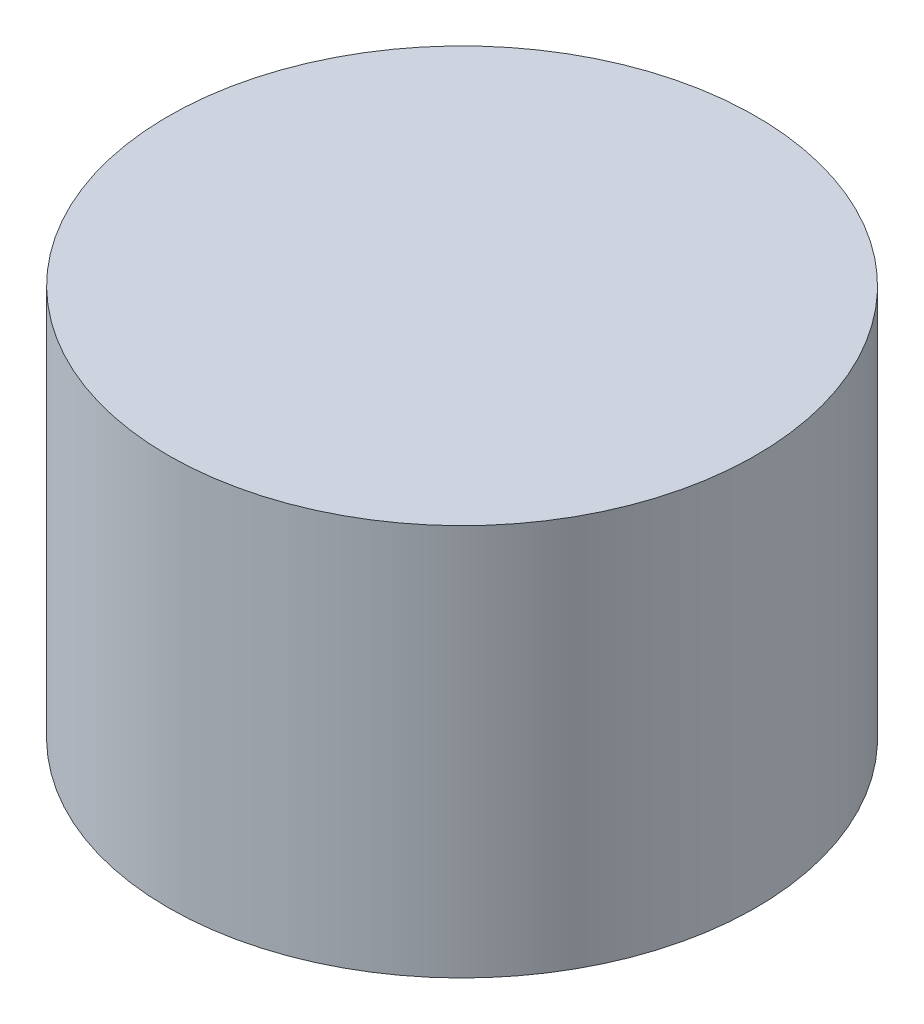
SolidWorks part; units mm, degrees
ref_plane "Front Plane" through (0, 0, 0) normal (0, 0, 1) x (1, 0, 0)
ref_plane "Top Plane" through (0, 0, 0) normal (0, 1, 0) x (1, 0, 0)
ref_plane "Right Plane" through (0, 0, 0) normal (1, 0, 0) x (0, 0, -1)
sketch "Sketch1" plane through (0, 0, 0) normal (0, 1, 0) x (1, 0, 0)
  circle A0 centre (0, 0) radius 12.75
  dimension "D1" = 25.5
extrude "Boss-Extrude1" add sketch "Sketch1" along normal blind 17
